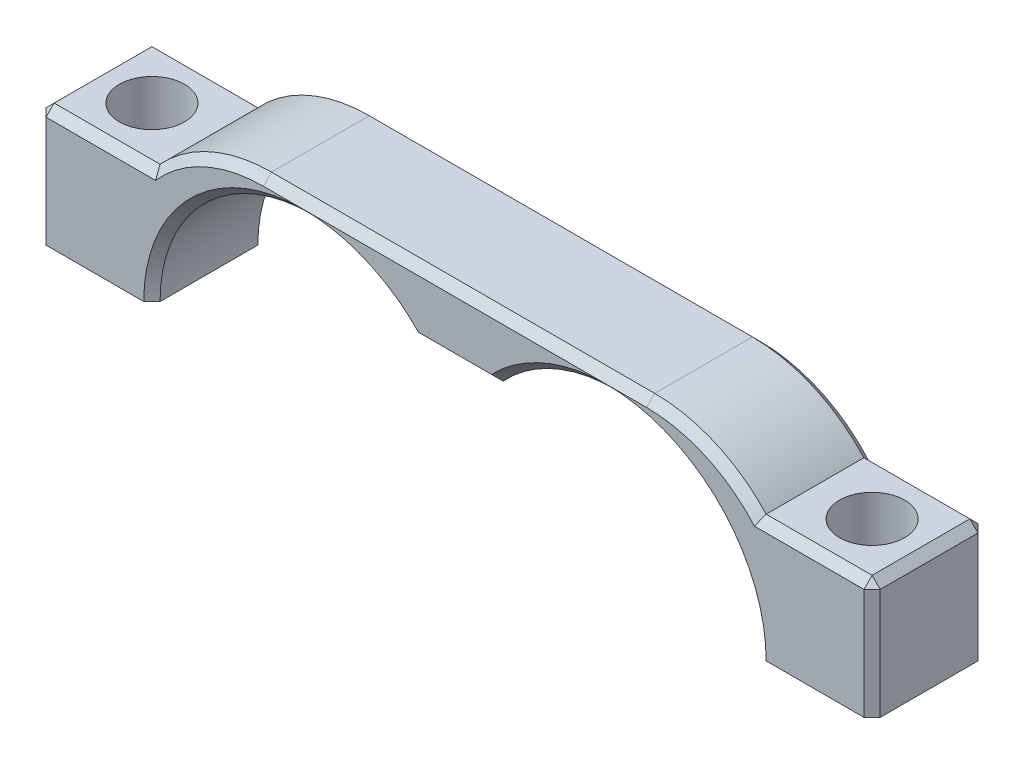
SolidWorks part; units mm, degrees
material "PLA"
ref_plane "Alzado" through (0, 0, 0) normal (0, 0, 1) x (1, 0, 0)
ref_plane "Planta" through (0, 0, 0) normal (0, 1, 0) x (1, 0, 0)
ref_plane "Vista lateral" through (0, 0, 0) normal (1, 0, 0) x (0, 0, -1)
sketch "Croquis1" plane through (0, 0, 0) normal (0, 0, 1) x (1, 0, 0)
  line L0 (2.4589, 6.3) -> (-2.4589, 6.3)
  line L1 (18.6, 10.3) -> (18.6, 7.3)
  line L2 (-18.6, 10.3) -> (18.6, 10.3)
  line L3 (18.6, 7.3) -> (25.6, 7.3)
  line L4 (25.6, 7.3) -> (25.6, 0)
  line L5 (0, 0) -> (0, 50000) construction
  line L6 (-25.6, 0) -> (-18.6, 0)
  line L7 (25.6, 0) -> (18.6, 0)
  line L8 (-25.6, 7.3) -> (-25.6, 0)
  line L9 (-18.6, 7.3) -> (-25.6, 7.3)
  line L10 (-18.6, 10.3) -> (-18.6, 7.3)
  arc A0 (18.6, 0) -> (2.4589, 6.3) centre (9.3, 0) ccw
  arc A1 (-18.6, 0) -> (-2.4589, 6.3) centre (-9.3, 0) cw
  point P4 (0, 0)
  point P14 (0, 6.3)
  point P19 (0, 6.3)
  point P21 (0, 10.3)
extrude "Saliente-Extruir1" add sketch "Croquis1" along normal blind 7
sketch "Croquis2" plane through (0, 7.3, 0) normal (0, 1, 0) x (1, 0, 0)
  circle A0 centre (22.1, -3.5) radius 2
  circle A1 centre (-22.1, -3.5) radius 2
extrude "Cortar-Extruir1" cut sketch "Croquis2" against normal up to surface (7.3 mm away) up to face at (-22.1, 0, 3.5)
fillet "Redondeo1" radius 9.3 2 edges at (-18.6, 10.3, 3.5) (18.6, 10.3, 3.5)
chamfer "Chaflán1" distance 0.5 angle 45 22 edges at (12.6814, 8.6635, 0) (0, 6.3, 0) (-12.6814, 8.6635, 0) (12.6814, 8.6635, 7) (0, 6.3, 7) (-12.6814, 8.6635, 7) (15.4939, 9.517, 0) (-15.4939, 9.517, 0) (0, 10.3, 0) (15.4939, 9.517, 7) (-15.4939, 9.517, 7) (0, 10.3, 7) (22.1, 7.3, 0) (25.6, 3.65, 0) (25.6, 7.3, 3.5) (22.1, 7.3, 7) (25.6, 3.65, 7) (-22.1, 7.3, 0) (-22.1, 7.3, 7) (-25.6, 3.65, 0) (-25.6, 7.3, 3.5) (-25.6, 3.65, 7)
